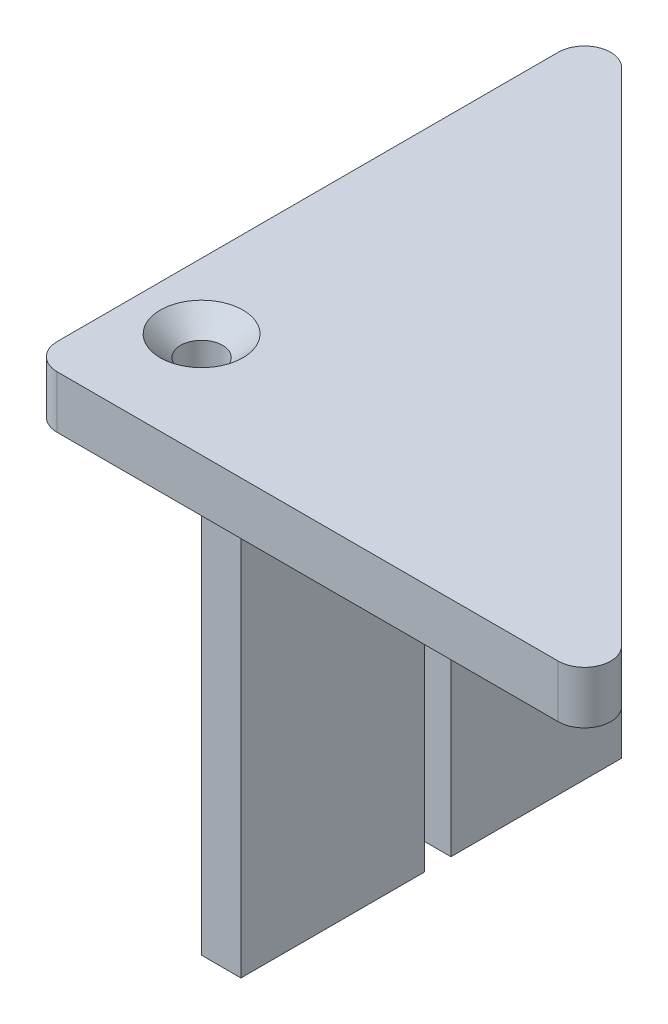
SolidWorks part; units mm, degrees
ref_plane "Płaszczyzna przednia" through (0, 0, 0) normal (0, 0, 1) x (1, 0, 0)
ref_plane "Płaszczyzna górna" through (0, 0, 0) normal (0, 1, 0) x (1, 0, 0)
ref_plane "Płaszczyzna prawa" through (0, 0, 0) normal (1, 0, 0) x (0, 0, -1)
sketch "Sketch1" plane through (0, 0, 0) normal (0, 1, 0) x (1, 0, 0)
  line L0 (-22.8113, 22.8113) -> (22.1887, -22.1887)
  line L2 (-22.8113, 22.8113) -> (-22.8113, -22.1887)
  line L3 (-22.8113, -22.1887) -> (22.1887, -22.1887)
  line L5 (-22.8113, 22.8113) -> (22.1887, -22.1887) construction
  line L6 (-22.8113, -22.1887) -> (0, 0) construction
  circle A0 centre (-17.8113, -14.1887) radius 1.6
  point P0 (0, 0)
  point P10 (-16.6388, -10.1785)
  dimension "D3" = 8
  dimension "D1" = 45
  dimension "D2" = 45
  dimension "D4" = 5
extrude "Boss-Extrude1" add sketch "Sketch1" along normal blind 4
sketch "Sketch2" plane through (0, 4, 0) normal (0, 1, 0) x (1, 0, 0)
  point P0 (-17.8113, -14.1887)
hole_wizard "CSK for M3 Countersunk Flat Head Screw1" positions "Sketch2" profile "Sketch3" countersink size "M3" standard "ISO" end condition through all
sketch "Sketch3" plane through (-17.8113, 4, 14.1887) normal (1, 0, 0) x (0, 0, 1)
  line L0 (0, 0) -> (0, 4)
  line L1 (0, 4) -> (1.6, 4)
  line L2 (1.6, 4) -> (1.6, 1.55)
  line L3 (1.6, 1.55) -> (3.15, 0)
  line L5 (3.15, 0) -> (0, 0)
  line L6 (-1.6, 1.55) -> (-3.15, 0) construction
  line L11 (0, -6.35) -> (0, 107.95) construction
  dimension "Thru Hole Dia." = 3.2
  dimension "Thru Hole Depth" = 4
  dimension "Near C'Sink Dia." = 6.3
  dimension "Near C'Sink Angle" = 90
fillet "Fillet1" radius 2 3 edges at (-22.8113, 2, 22.1887) (22.1887, 2, 22.1887) (-22.8113, 2, -22.8113)
sketch "Sketch5" plane through (0, 0, 0) normal (0, -1, 0) x (1, 0, 0)
  line L0 (-12.8113, 5.5582) -> (-12.8113, -12.8113)
  line L1 (18.7745, 18.7745) -> (-19.3971, -19.3971) construction
  line L2 (-22.8113, -17.9829) -> (-22.8113, 20.1887) construction
  line L3 (-9.8113, -9.8113) -> (-12.8113, -12.8113)
  line L5 (-12.8113, -12.8113) -> (-12.8113, 19.1887)
  line L6 (-12.8113, 19.1887) -> (-9.8113, 19.1887)
  line L7 (-9.8113, -9.8113) -> (-9.8113, 19.1887)
  line L8 (-20.8113, 22.1887) -> (17.3603, 22.1887) construction
  line L9 (-12.8113, 19.1887) -> (-12.8113, 5.5582)
  line L10 (-12.8113, 5.1887) -> (-9.8113, 5.1887)
  line L11 (-12.8113, 3.1887) -> (-9.8113, 3.1887)
  line L12 (-9.8113, -9.8113) -> (-12.8113, -12.8113)
  line L13 (-12.8113, -12.8113) -> (-9.8113, -9.8113)
  line L14 (-12.8113, -12.8113) -> (-9.8113, -9.8113)
  line L15 (-9.8113, -9.8113) -> (-12.8113, -9.8113)
  dimension "D1" = 10
  dimension "D2" = 3
  dimension "D3" = 3
  dimension "D4" = 17
  dimension "D5" = 2
extrude "Boss-Extrude2" add sketch "Sketch5" along normal blind 32 contours L0 L10 L7 L6 L5 | L15 L7 L11 L0 region at (-11.3113, 0, 12.1887) region at (-11.3113, 0, -3.3113)
